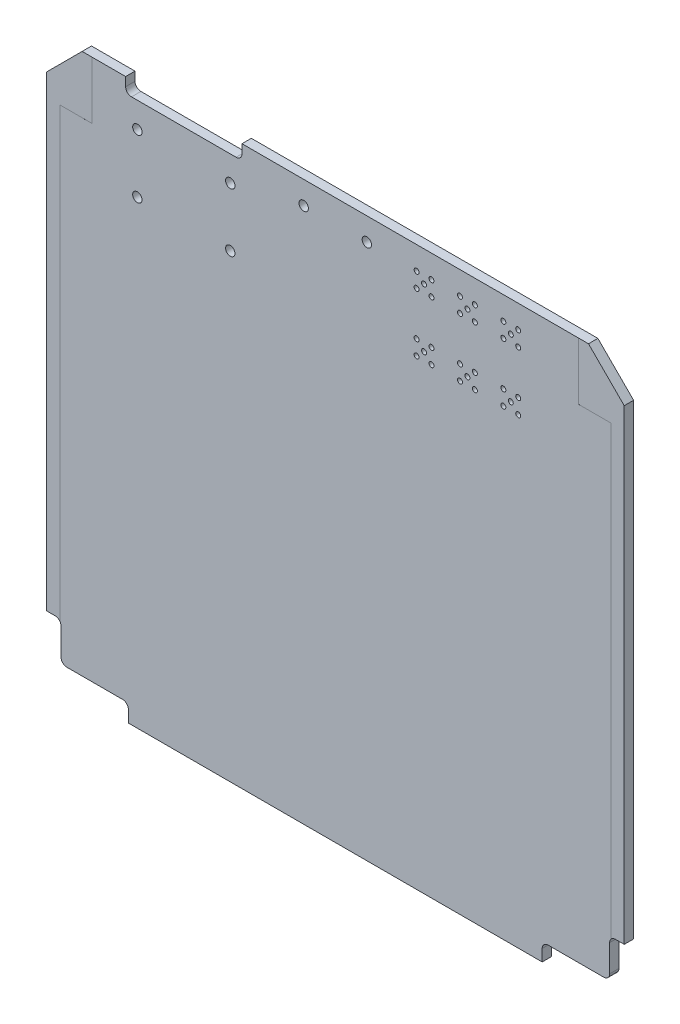
SolidWorks part; units mm, degrees
material "Oshpark board"
ref_plane "Front Plane" through (0, 0, 0) normal (0, 0, 1) x (1, 0, 0)
ref_plane "Top Plane" through (0, 0, 0) normal (0, 1, 0) x (1, 0, 0)
ref_plane "Right Plane" through (0, 0, 0) normal (1, 0, 0) x (0, 0, -1)
ref_plane "Plane4" through (0, 0, -0.0125) normal (0, 0, -1) x (-1, 0, 0)
sketch "Sketch1" plane through (0, 0, -0.0125) normal (0, 0, -1) x (-1, 0, 0)
  line L0 (35.3, -50) -> (35.3, -48)
  line L1 (36.3, -47) -> (45.8, -47)
  line L2 (46.8, -46) -> (46.8, -41.4)
  line L3 (47.8, -40.4) -> (49.3, -40.4)
  line L4 (49.3, -40.4) -> (49.3, 39.2)
  line L5 (49.3, 39.2) -> (43.2, 45.3)
  line L6 (43.2, 45.3) -> (35.5, 45.3)
  line L7 (35.5, 45.3) -> (35.5, 43.8) construction
  line L8 (34.5, 42.8) -> (4.5, 42.8) construction
  line L9 (3.5, 43.8) -> (3.5, 45.3) construction
  line L10 (3.5, 45.3) -> (-43.2, 45.3)
  line L11 (-43.2, 45.3) -> (-49.3, 39.2)
  line L12 (-49.3, 39.2) -> (-49.3, -40.4)
  line L13 (-49.3, -40.4) -> (-47.8, -40.4)
  line L14 (-46.8, -41.4) -> (-46.8, -46)
  line L15 (-45.8, -47) -> (-36.3, -47)
  line L16 (-35.3, -48) -> (-35.3, -50)
  line L17 (-35.3, -50) -> (35.3, -50)
  line L18 (0, -50) -> (0, 45.3) construction
  line L19 (19.5, 42.8) -> (19.5, 25.5258) construction
  line L20 (-13.87, 41.37) -> (-16.41, 38.83) construction
  line L21 (-21.27, 41.37) -> (-23.81, 38.83) construction
  line L22 (-28.67, 41.37) -> (-31.21, 38.83) construction
  line L23 (35.5, 45.3) -> (3.5, 45.3)
  arc A0 (35.3, -48) -> (36.3, -47) centre (36.3, -48) cw
  arc A1 (45.8, -47) -> (46.8, -46) centre (45.8, -46) ccw
  arc A2 (46.8, -41.4) -> (47.8, -40.4) centre (47.8, -41.4) cw
  arc A3 (35.5, 43.8) -> (34.5, 42.8) centre (34.5, 43.8) cw construction
  arc A4 (4.5, 42.8) -> (3.5, 43.8) centre (4.5, 43.8) cw construction
  arc A5 (-47.8, -40.4) -> (-46.8, -41.4) centre (-47.8, -41.4) cw
  arc A6 (-46.8, -46) -> (-45.8, -47) centre (-45.8, -46) ccw
  arc A7 (-36.3, -47) -> (-35.3, -48) centre (-36.3, -48) cw
  circle A8 centre (-21.27, 41.37) radius 0.425
  circle A9 centre (-23.81, 41.37) radius 0.425
  circle A10 centre (-22.54, 40.1) radius 0.425
  circle A11 centre (-13.87, 41.37) radius 0.425
  circle A12 centre (-23.81, 38.83) radius 0.425
  circle A13 centre (-16.41, 41.37) radius 0.425
  circle A14 centre (-15.14, 40.1) radius 0.425
  circle A15 centre (-21.27, 38.83) radius 0.425
  circle A16 centre (-28.67, 41.37) radius 0.425
  circle A17 centre (-31.21, 41.37) radius 0.425
  circle A18 centre (-16.41, 38.83) radius 0.425
  circle A19 centre (-29.94, 40.1) radius 0.425
  circle A20 centre (-31.21, 38.83) radius 0.425
  circle A21 centre (-28.67, 38.83) radius 0.425
  circle A22 centre (33.775, 38.54) radius 0.8 construction
  circle A23 centre (5.225, 38.54) radius 0.8 construction
  circle A24 centre (-13.87, 38.83) radius 0.425
  point P35 (-15.14, 40.1)
  dimension "D7" = 2.5
  dimension "D8" = 1.6
  dimension "D9" = 14.275
  dimension "D10" = 4.26
  dimension "D11" = 1
  dimension "D12" = 1
  dimension "D13" = 1
  dimension "D14" = 1
  dimension "D15" = 1
  dimension "D16" = 1
  dimension "D17" = 1
  dimension "D18" = 1
  dimension "D26" = 0.85
  dimension "D1" = 98.6
  dimension "D2" = 95.3
  dimension "D3" = 14
  dimension "D4" = 9.6
  dimension "D5" = 2.5
  dimension "D6" = 3
  dimension "D19" = 14
  dimension "D20" = 2.5
  dimension "D21" = 6.1
  dimension "D22" = 6.1
  dimension "D23" = 32
  dimension "D24" = 2.54
  dimension "D25" = 2.54
  dimension "D28" = 7.4
  dimension "D29" = 3.93
  dimension "D30" = 35.43
  dimension "D31" = 45
  dimension "D32" = 45
  dimension "D33" = 29.8
  dimension "D34" = 50
  dimension "D27" = 3
extrude "Boss-Extrude1" add sketch "Sketch1" against normal blind 1.6
sketch "thermalContacts_lower" plane through (0, 0, -0.0125) normal (0, 0, -1) x (-1, 0, 0)
  line L0 (47, 35.5) -> (47, -41.5) construction
  line L1 (41.5, 35.5) -> (41.5, 41.5) construction
  line L2 (41.5, 35.5) -> (47, 35.5) construction
  line L3 (47, 35.5) -> (47, -41.5)
  line L4 (41.5, 35.5) -> (41.5, 41.5)
  line L5 (41.5, 35.5) -> (47, 35.5)
  line L6 (-47, 35.5) -> (-47, -41.5) construction
  line L7 (-41.5, 35.5) -> (-47, 35.5) construction
  line L8 (-41.5, 35.5) -> (-41.5, 41.5) construction
  line L9 (-47, 35.5) -> (-47, -41.5)
  line L10 (-41.5, 35.5) -> (-47, 35.5)
  line L11 (-41.5, 35.5) -> (-41.5, 41.5)
  line L12 (-41.5, 41.5) -> (-41.5, 47) construction
  line L13 (-41.5, 41.5) -> (-49.5, 41.5) construction
  line L14 (-41.5, 41.5) -> (-41.5, 47)
  line L15 (-41.5, 41.5) -> (-49.5, 41.5) construction
  line L16 (41.5, 41.5) -> (41.5, 47) construction
  line L17 (41.5, 41.5) -> (49.5, 41.5) construction
  line L18 (41.5, 41.5) -> (41.5, 47)
  line L19 (41.5, 41.5) -> (49.5, 41.5) construction
  line L20 (47, -41.5) -> (59.8273, -41.5)
  line L21 (59.8273, -41.5) -> (59.8273, 47)
  line L22 (-56.1922, 47) -> (-41.5, 47)
  line L23 (41.5, 47) -> (59.8273, 47)
  line L24 (-56.1922, 47) -> (-56.1922, -41.5)
  line L25 (-47, -41.5) -> (-56.1922, -41.5)
sketch "thermalContacts_upper" plane through (0, 0, 1.5875) normal (0, 0, 1) x (1, 0, 0)
  line L3 (-47, 35.5) -> (-47, -41.5)
  line L4 (-41.5, 35.5) -> (-41.5, 41.5)
  line L5 (-41.5, 35.5) -> (-47, 35.5)
  line L9 (47, 35.5) -> (47, -41.5)
  line L10 (41.5, 35.5) -> (47, 35.5)
  line L11 (41.5, 35.5) -> (41.5, 41.5)
  line L14 (41.5, 41.5) -> (41.5, 47)
  line L15 (41.5, 41.5) -> (49.5, 41.5) construction
  line L18 (-41.5, 41.5) -> (-41.5, 47)
  line L19 (-41.5, 41.5) -> (-49.5, 41.5) construction
  line L20 (47, -41.5) -> (59.8273, -41.5)
  line L21 (59.8273, -41.5) -> (59.8273, 47)
  line L22 (59.8273, 47) -> (41.5, 47)
  line L23 (-41.5, 47) -> (-56.1922, 47)
  line L24 (-56.1922, 47) -> (-56.1922, -41.5)
  line L25 (-56.1922, -41.5) -> (-47, -41.5)
pattern_linear "LPattern2" count 2 spacing 10 along (0, -1, 0) of face at (14.295, 41.37, 1.5875) of face at (14.295, 38.83, 1.5875) of face at (15.565, 40.1, 1.5875) of face at (16.835, 38.83, 1.5875) of face at (21.695, 41.37, 1.5875) of face at (21.695, 38.83, 1.5875) of face at (22.965, 40.1, 1.5875) of face at (24.235, 38.83, 1.5875) of face at (24.235, 41.37, 1.5875) of face at (16.835, 41.37, 1.5875) of face at (29.095, 41.37, 1.5875) of face at (29.095, 38.83, 1.5875) of face at (30.365, 40.1, 1.5875) of face at (31.635, 38.83, 1.5875) of face at (31.635, 41.37, 1.5875)
extrude "slotFootprints_REF" cut sketch "thermalContacts_lower" against normal blind 0.0001
extrude "slotFootprints" cut sketch "thermalContacts_upper" against normal blind 0.0001
sketch "Sketch2" plane through (0, 0, 1.5875) normal (0, 0, 1) x (1, 0, 0)
  line L1 (-41.5, 45.3) -> (41.5, 45.3) construction
  line L2 (-49.3, -40.4) -> (-49.3, 39.2) construction
  line L3 (-35.775, 45.3) -> (-35.775, 43.8)
  line L4 (-41.5, 45.3) -> (41.5, 45.3) construction
  line L5 (-34.775, 42.8) -> (-16.925, 42.8)
  line L6 (-15.925, 43.8) -> (-15.925, 45.3)
  line L7 (-15.925, 45.3) -> (-35.775, 45.3)
  arc A1 (-16.925, 42.8) -> (-15.925, 43.8) centre (-16.925, 43.8) ccw
  arc A2 (-35.775, 43.8) -> (-34.775, 42.8) centre (-34.775, 43.8) ccw
  circle A3 centre (-33.775, 38.4723) radius 0.8
  circle A4 centre (-17.925, 38.4723) radius 0.8
  circle A5 centre (-17.925, 28.4723) radius 0.8
  circle A6 centre (-33.775, 28.4723) radius 0.8
  dimension "D2" = 1.6
  dimension "D5" = 1
  dimension "D1" = 15.85
  dimension "D3" = 6.8277
  dimension "D4" = 15.525
  dimension "D6" = 2
  dimension "D7" = 2
  dimension "D8" = 2.5
  dimension "D10" = 10
  dimension "D9" = 2
extrude "20pin_mounts" cut sketch "Sketch2" against normal through all
sketch "Sketch3" plane through (0, 0, -0.0125) normal (0, 0, -1) x (-1, 0, 0)
  line L0 (-49.3, -40.4) -> (-49.3, 39.2) construction
  line L3 (15.925, 45.3) -> (-41.5, 45.3) construction
  circle A2 centre (5.39, 41.4) radius 0.8
  circle A3 centre (-5.38, 41.4) radius 0.8
  point P6 (0, 0)
  point P7 (-3.4545, 42.2782)
  point P8 (-5.38, 42.2782)
  point P11 (0, 0)
  dimension "D1" = 1.6
  dimension "D2" = 10.77
  dimension "D3" = 43.92
  dimension "D4" = 3.9
extrude "12pin_mounts" cut sketch "Sketch3" against normal blind 10
